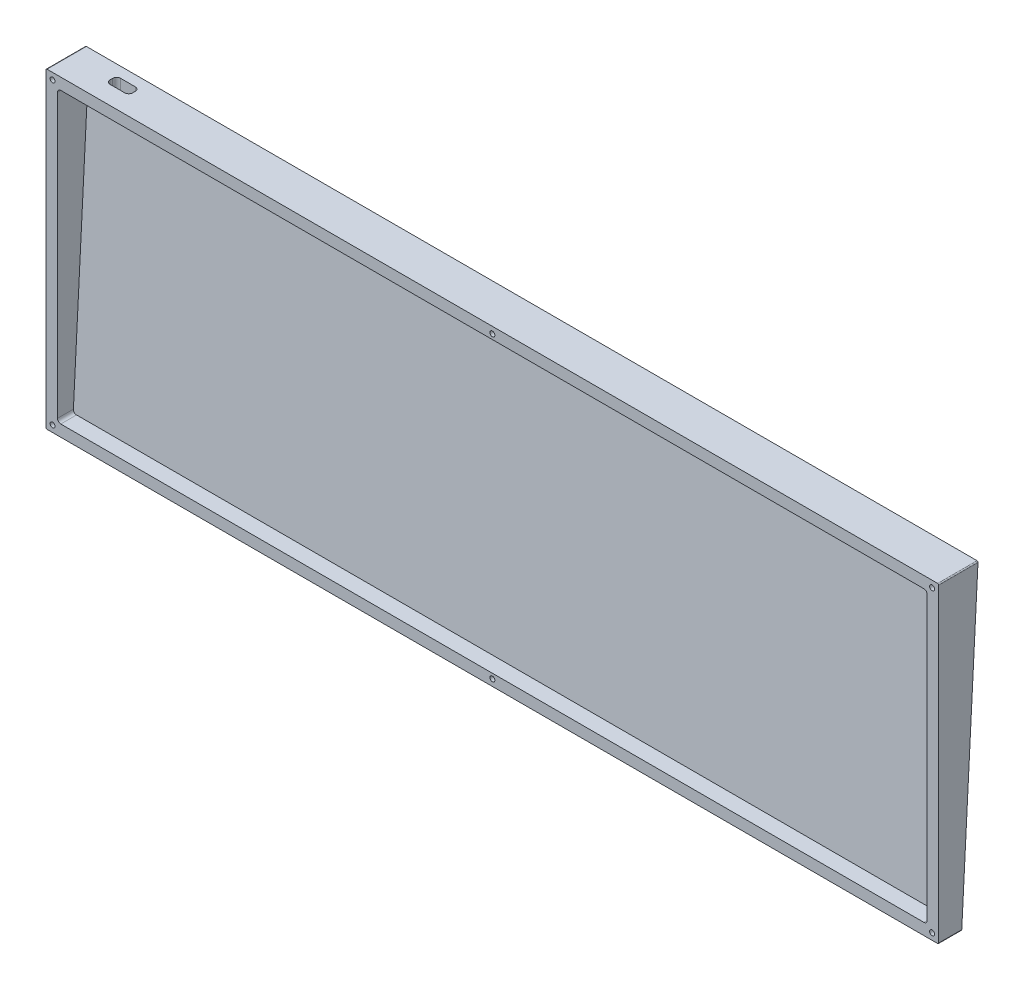
SolidWorks part; units mm, degrees
material "Mahogany"
ref_plane "Front Plane" through (0, 0, 0) normal (0, 0, 1) x (1, 0, 0)
ref_plane "Top Plane" through (0, 0, 0) normal (0, 1, 0) x (1, 0, 0)
ref_plane "Right Plane" through (0, 0, 0) normal (1, 0, 0) x (0, 0, -1)
sketch "Sketch3" plane through (0, 0, 0) normal (0, 0, 1) x (1, 0, 0)
  line L33 (-40.4842, 142.4008) -> (-40.4842, 2.6341)
  line L35 (380.2065, 142.4008) -> (380.2065, 2.6341)
  line L36 (157.1611, 2.6341) -> (182.5611, 2.6341)
  line L37 (157.1611, 142.4008) -> (182.5611, 142.4008)
  line L40 (182.5611, 142.4008) -> (182.5611, 2.6341)
  line L41 (-40.4842, 142.4008) -> (157.1611, 142.4008)
  line L42 (-40.4842, 142.4008) -> (-40.4842, 2.6341)
  line L43 (-40.4842, 2.6341) -> (157.1611, 2.6341)
  line L44 (157.1611, 142.4008) -> (157.1611, 2.6341)
  line L45 (182.5611, 2.6341) -> (380.2065, 2.6341)
  line L46 (182.5611, 2.6341) -> (182.5611, 142.4008)
  line L47 (182.5611, 142.4008) -> (380.2065, 142.4008)
  line L48 (380.2065, 2.6341) -> (380.2065, 142.4008)
  line L49 (168.0831, 144.7805) -> (171.6391, 144.7805) construction
  line L54 (168.0831, 146.8125) -> (171.6391, 146.8125)
  line L55 (168.0831, 142.7485) -> (171.6391, 142.7485)
  line L56 (-43.3591, -0.2408) -> (-40.8446, 2.2737) construction
  line L57 (-44.796, 1.1961) -> (-42.2815, 3.7105)
  line L58 (-41.9223, -1.6776) -> (-39.4078, 0.8368)
  line L59 (380.5669, 142.7612) -> (383.0814, 145.2757) construction
  line L60 (379.13, 144.1981) -> (381.6445, 146.7125)
  line L61 (382.0037, 141.3244) -> (384.5182, 143.8388)
  line L62 (-43.3591, 145.2757) -> (-40.8446, 142.7612) construction
  line L63 (-41.9223, 146.7125) -> (-39.4078, 144.1981)
  line L64 (-44.796, 143.8388) -> (-42.2815, 141.3244)
  line L65 (168.0831, 0.2545) -> (171.6391, 0.2545) construction
  line L66 (168.0831, 2.2865) -> (171.6391, 2.2865)
  line L67 (168.0831, -1.7775) -> (171.6391, -1.7775)
  line L68 (380.5669, 2.2737) -> (383.0814, -0.2408) construction
  line L69 (382.0037, 3.7105) -> (384.5182, 1.1961)
  line L70 (379.13, 0.8368) -> (381.6445, -1.6776)
  line L2576 (385.7611, 147.9555) -> (-46.0389, 147.9555)
  line L2581 (-46.0389, 147.9555) -> (-46.0389, -2.9205)
  line L2582 (385.7611, -2.9205) -> (-46.0389, -2.9205)
  line L2583 (385.7611, 147.9555) -> (385.7611, -2.9205)
  line L2593 (380.2065, 142.4008) -> (-40.4842, 142.4008) construction
  line L2594 (380.2065, 2.6341) -> (-40.4842, 2.6341) construction
  arc A5 (168.0831, 146.8125) -> (168.0831, 142.7485) centre (168.0831, 144.7805) ccw
  arc A6 (171.6391, 142.7485) -> (171.6391, 146.8125) centre (171.6391, 144.7805) ccw
  arc A7 (-44.796, 1.1961) -> (-41.9223, -1.6776) centre (-43.3591, -0.2408) ccw
  arc A8 (-39.4078, 0.8368) -> (-42.2815, 3.7105) centre (-40.8446, 2.2737) ccw
  arc A9 (379.13, 144.1981) -> (382.0037, 141.3244) centre (380.5669, 142.7612) ccw
  arc A10 (384.5182, 143.8388) -> (381.6445, 146.7125) centre (383.0814, 145.2757) ccw
  arc A11 (-41.9223, 146.7125) -> (-44.796, 143.8388) centre (-43.3591, 145.2757) ccw
  arc A12 (-42.2815, 141.3244) -> (-39.4078, 144.1981) centre (-40.8446, 142.7612) ccw
  arc A13 (168.0831, 2.2865) -> (168.0831, -1.7775) centre (168.0831, 0.2545) ccw
  arc A14 (171.6391, -1.7775) -> (171.6391, 2.2865) centre (171.6391, 0.2545) ccw
  arc A15 (382.0037, 3.7105) -> (379.13, 0.8368) centre (380.5669, 2.2737) ccw
  arc A16 (381.6445, -1.6776) -> (384.5182, 1.1961) centre (383.0814, -0.2408) ccw
  text T0 ".0625\" radius fillet inside\r\n"
  point P2 (169.8611, 144.7805)
  point P3 (382.5861, 144.7805)
  point P4 (169.8611, 0.2545)
  point P5 (382.5861, 0.2545)
  point P7 (169.8611, 144.7805)
  point P9 (169.8611, -2.9205)
  point P13 (169.8611, 147.9555)
  point P17 (-42.1019, 1.0165)
  point P23 (381.8241, 144.0185)
  point P31 (-42.1019, 144.0185)
  point P39 (169.8611, 0.2545)
  point P44 (381.8241, 1.0165)
  point P57 (0, 0)
  point P2589 (-42.8639, 144.7805)
  point P2594 (-42.8639, 0.2545)
  dimension "D3" = 3.175
  dimension "D4" = 0
  dimension "D6" = 3.175
  dimension "D7" = 4.064
  dimension "D8" = 7.62
  dimension "D5" = 3.175
  dimension "D14" = 3.175
  dimension "D15" = 3.175
  dimension "D16" = 3.175
  dimension "D17" = 3.175
  dimension "D18" = 0
  dimension "D19" = 3.175
  dimension "D20" = 3.175
  dimension "D22" = 3.175
  dimension "D32" = 25.4
  dimension "D33" = 12.7
sketch "Sketch4" plane through (0, 0, 0) normal (0, 0, 1) x (1, 0, 0)
  line L164 (277.1382, 43.9218) -> (277.1382, 24.872)
  line L165 (277.1382, 24.872) -> (258.0882, 24.872)
  line L166 (258.0882, 24.872) -> (258.0882, 5.8192)
  line L167 (258.0882, 5.8192) -> (315.2412, 5.8192)
  line L168 (315.2412, 5.8192) -> (315.2412, 24.872)
  line L169 (315.2412, 24.872) -> (296.1912, 24.872)
  line L170 (296.1912, 24.872) -> (296.1912, 43.9218)
  line L171 (296.1912, 43.9218) -> (277.1382, 43.9218)
  line L172 (300.9522, 143.9325) -> (300.9522, 29.6331)
  line L173 (300.9522, 29.6331) -> (320.0022, 29.6331)
  line L174 (320.0022, 29.6331) -> (320.0022, 10.5817)
  line L175 (320.0022, 10.5817) -> (377.1522, 10.5817)
  line L176 (377.1522, 10.5817) -> (377.1522, 143.9325)
  line L177 (377.1522, 143.9325) -> (300.9522, 143.9325)
  line L178 (5.6773, 105.8325) -> (5.6773, 67.7343)
  line L179 (5.6773, 67.7343) -> (5.6759, 67.7343)
  line L180 (5.6759, 67.7343) -> (5.6759, 29.6331)
  line L181 (5.6759, 29.6331) -> (5.6773, 29.6331)
  line L182 (5.6773, 29.6331) -> (5.6773, 10.5817)
  line L183 (5.6773, 10.5817) -> (253.3272, 10.5817)
  line L184 (253.3272, 10.5817) -> (253.3272, 29.6331)
  line L185 (253.3272, 29.6331) -> (272.3782, 29.6331)
  line L186 (272.3782, 29.6331) -> (272.3782, 48.6829)
  line L187 (272.3782, 48.6829) -> (291.4282, 48.6829)
  line L188 (291.4282, 48.6829) -> (291.4282, 105.8325)
  line L189 (291.4282, 105.8325) -> (5.6773, 105.8325)
  line L230 (215.2272, 143.9325) -> (291.4282, 143.9325)
  line L231 (291.4282, 143.9325) -> (291.4282, 124.8815)
  line L232 (291.4282, 124.8815) -> (215.2272, 124.8815)
  line L233 (215.2272, 124.8815) -> (215.2272, 143.9325)
  line L234 (129.5012, 143.9325) -> (205.7032, 143.9325)
  line L235 (205.7032, 143.9325) -> (205.7032, 124.8815)
  line L236 (205.7032, 124.8815) -> (129.5012, 124.8815)
  line L237 (129.5012, 124.8815) -> (129.5012, 143.9325)
  line L238 (43.7774, 143.9325) -> (119.9782, 143.9325)
  line L239 (119.9782, 143.9325) -> (119.9782, 124.8815)
  line L240 (119.9782, 124.8815) -> (43.7774, 124.8815)
  line L241 (43.7774, 124.8815) -> (43.7774, 143.9325)
  line L242 (5.6773, 143.9325) -> (24.7286, 143.9325)
  line L243 (24.7286, 143.9325) -> (24.7286, 124.8815)
  line L244 (24.7286, 124.8815) -> (5.6773, 124.8815)
  line L245 (5.6773, 124.8815) -> (5.6773, 143.9325)
  point P0 (15.2029, 134.407)
extrude "Boss-Extrude2" add sketch "Sketch3" along normal blind 19.05 contours L2576 L2581 L2582 L2583
sketch "Sketch11" plane through (-46.0389, 0, 0) normal (-1, 0, 0) x (0, 0, 1)
  line L0 (-0.132, 150.4735) -> (2613.0796, -49712.5738)
  line L1 (3.6728, 150.6729) -> (2616.8844, -49712.3744)
  line L2 (0, 147.9555) -> (19.05, 147.9555)
  line L4 (0, 147.9555) -> (0, -2.9205)
  line L5 (0, -2.9205) -> (19.05, -2.9205)
  line L6 (19.05, 147.9555) -> (19.05, -2.9205)
  line M1 (0, 147.9555) -> (0, -2.9205)
  line M2 (0, -2.9205) -> (19.05, -2.9205)
  line M4 (19.05, 147.9555) -> (0, 147.9555)
  dimension "D1" = 3.81
extrude "Cut-Extrude4" cut sketch "Sketch11" against normal through all contours L0 M1 M2 region at (-46.0389, 47.3715, 2.6357)
extrude "Cut-Extrude5" cut sketch "Sketch3<25>" against normal through all and the other way through all contours L47 L40 L45 L35 | L37 L44 L36 L40 | L44 L41 L33 L43 | L33 A12 L41 | L43 A8 L42 | L35 A15 L45 | L47 A9 L35 region at (-39.8253, 141.7419, 0) region at (58.3521, 72.5175, 0) region at (-39.8253, 3.2931, 0) region at (169.8611, 72.5175, 0) region at (281.3702, 72.5175, 0) region at (379.5475, 141.7419, 0) region at (379.5475, 3.2931, 0)
sketch "Sketch3<25>" plane through (0, 0, 0) normal (0, 0, 1) x (1, 0, 0) same geometry as "Sketch3"
extrude "Boss-Extrude3" add sketch "Sketch11<3>" against normal through all contours L1 L0 M4 M2 region at (-46.0389, 72.5175, 5.8612)
sketch "Sketch11<3>" plane through (-46.0389, 0, 0) normal (-1, 0, 0) x (0, 0, 1) same geometry as "Sketch11"
hole_wizard "M2 Clearance Hole1" positions "Sketch16" profile "Sketch17" hole size "M2" standard "ANSI Metric" end condition through all
sketch "Sketch16" plane through (0, 0, 19.05) normal (0, 0, 1) x (1, 0, 0)
  point P0 (-42.8639, 144.7805)
  point P3 (169.8611, 144.7805)
  point P6 (382.5861, 144.7805)
  point P9 (382.5861, 0.2545)
  point P12 (169.8611, 0.2545)
  point P15 (-42.8639, 0.2545)
sketch "Sketch17" plane through (-42.8639, 144.7805, 19.05) normal (1, 0, 0) x (0, -1, 0)
  line L0 (0, 0) -> (0, 19.05)
  line L1 (0, 19.05) -> (1.2, 19.05)
  line L2 (1.2, 19.05) -> (1.2, 0)
  line L5 (1.2, 0) -> (0, 0)
  line L11 (0, -6.35) -> (0, 107.95) construction
  dimension "Thru Hole Dia." = 2.4
  dimension "Thru Hole Depth" = 19.05
extrude "Cut-Extrude8" cut sketch "Sketch3<27>" along normal blind 10.16 contours L70 A16 L69 A15 | L67 A14 L66 A13 | L58 A8 L57 A7
sketch "Sketch3<27>" plane through (0, 0, 0) normal (0, 0, 1) x (1, 0, 0) same geometry as "Sketch3"
extrude "Cut-Extrude9" cut sketch "Sketch3<28>" along normal blind 2.032 contours L55 A6 L54 A5 | L60 A10 L61 A9 | L64 A12 L63 A11 region at (169.8611, 144.7805, 0)
sketch "Sketch3<28>" plane through (0, 0, 0) normal (0, 0, 1) x (1, 0, 0) same geometry as "Sketch3"
fillet "Fillet7" radius 1.5875 4 edges at (380.2065, 2.6341, 15.2406) (380.2065, 142.4008, 11.5782) (-40.4842, 2.6341, 15.2406) (-40.4842, 142.4008, 11.5782)
fillet "Fillet8" radius 0.508 4 edges at (-46.0389, -2.9205, 13.4785) (385.7611, -2.9205, 13.4785) (385.7611, 147.9555, 9.525) (-46.0389, 147.9555, 9.525)
sketch "Sketch18" plane through (0, 147.9555, 0) normal (0, 1, 0) x (1, 0, 0)
  line L1 (-16.8289, -10.16) -> (-23.9409, -10.16)
  line L2 (-14.9239, -8.255) -> (-14.9239, -6.985)
  line L3 (-16.8289, -5.08) -> (-23.9409, -5.08)
  line L4 (-25.8459, -8.255) -> (-25.8459, -6.985)
  line L5 (-46.0389, -19.05) -> (-46.0389, -0.0266) construction
  line L6 (385.2531, 0) -> (-45.5309, 0) construction
  arc A0 (-23.9409, -10.16) -> (-25.8459, -8.255) centre (-23.9409, -8.255) cw
  arc A1 (-23.9409, -5.08) -> (-25.8459, -6.985) centre (-23.9409, -6.985) ccw
  arc A2 (-14.9239, -6.985) -> (-16.8289, -5.08) centre (-16.8289, -6.985) ccw
  arc A3 (-16.8289, -10.16) -> (-14.9239, -8.255) centre (-16.8289, -8.255) ccw
  point P6 (-25.8459, -10.16)
  point P11 (-14.9239, -5.08)
  point P14 (-14.9239, -10.16)
  point P15 (-14.9239, -7.62)
  point P17 (-20.3849, -10.16)
  dimension "D3" = 1.905
  dimension "D1" = 10.922
  dimension "D2" = 5.08
  dimension "D4" = 7.62
  dimension "D5" = 25.654
extrude "Cut-Extrude10" cut sketch "Sketch18" against normal up to next contours L3 A1 L4 A0 L1 A3 L2 A2
